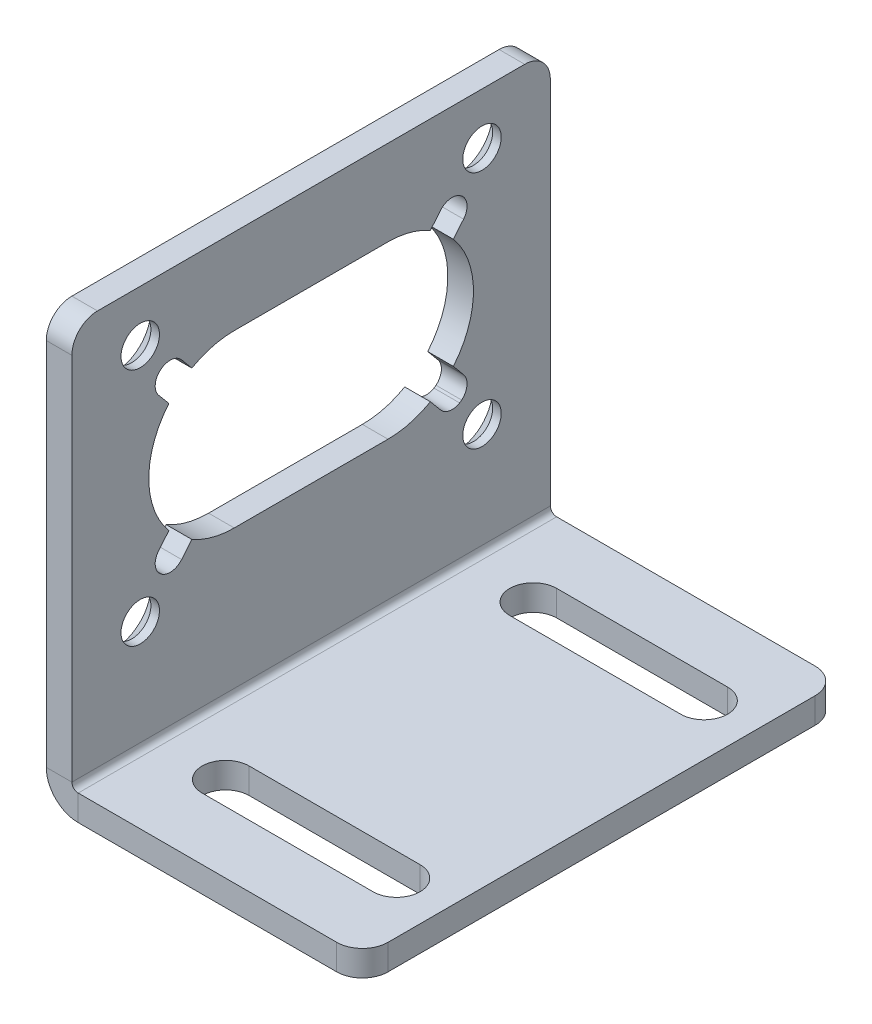
SolidWorks part; units mm, degrees
note: The reader was unsure of these and kept them because the rebuilt part matched: flange length of "Edge-Flange1".
material "0.6015 (EN-GJL-150)"
ref_plane "Front" through (0, 0, 0) normal (0, 0, 1) x (1, 0, 0)
ref_plane "Top" through (0, 0, 0) normal (0, 1, 0) x (1, 0, 0)
ref_plane "Right" through (0, 0, 0) normal (1, 0, 0) x (0, 0, -1)
sketch "Sketch1" plane through (0, 0, 0) normal (0, 1, 0) x (1, 0, 0)
  line L0 (-7.5, -18) -> (12.5, -18) construction
  line L1 (-18.5, 28) -> (15.5, 28)
  line L2 (-18.5, 28) -> (-18.5, -28)
  line L3 (-18.5, -28) -> (15.5, -28)
  line L4 (18.5, 25) -> (18.5, -25)
  line L5 (-18.5, 28) -> (18.5, -28) construction
  line L6 (-18.5, -28) -> (18.5, 28) construction
  line L7 (-7.5, -15.25) -> (12.5, -15.25)
  line L8 (-7.5, -20.75) -> (12.5, -20.75)
  line L9 (-54.4817, 0) -> (59.9128, 0) construction
  line L10 (-7.5, 18) -> (12.5, 18) construction
  line L11 (-7.5, 15.25) -> (12.5, 15.25)
  line L12 (-7.5, 20.75) -> (12.5, 20.75)
  arc A0 (15.5, -28) -> (18.5, -25) centre (15.5, -25) ccw
  arc A1 (15.5, 28) -> (18.5, 25) centre (15.5, 25) cw
  arc A2 (-7.5, -15.25) -> (-7.5, -20.75) centre (-7.5, -18) ccw
  arc A3 (12.5, -20.75) -> (12.5, -15.25) centre (12.5, -18) ccw
  arc A4 (-7.5, 15.25) -> (-7.5, 20.75) centre (-7.5, 18) cw
  arc A5 (12.5, 20.75) -> (12.5, 15.25) centre (12.5, 18) cw
  point P0 (0, 0)
  point P14 (2.5, -18)
  point P24 (2.5, 18)
  dimension "D3" = 3
  dimension "D1" = 37
  dimension "D2" = 56
  dimension "D4" = 36
  dimension "D5" = 5.5
  dimension "D6" = 20
  dimension "D7" = 11
base flange "Base-Flange1" sketch "Sketch1" thickness 3 reverse thickness direction no parameters "D1"=0.7366
edge flange "Edge-Flange1" sketch "Sketch4" flange angle 90 flange length 50 flange position material inside bend radius 0.7366 thickness 3 relief rectangular parameters "D6"=10
sketch "Sketch4" plane through (-18.5, 0, 0) normal (1, 0, 0) x (0, 0, -1)
  line L2 (-28, 0) -> (-28, 44)
  line L3 (-25, 47) -> (25, 47)
  line L4 (28, 44) -> (28, 0)
  line L5 (28, 0) -> (-28, 0) construction
  line L6 (28, 0) -> (-28, 0)
  line L7 (28, -3) -> (-28, -3) construction
  arc A0 (-28, 44) -> (-25, 47) centre (-25, 44) cw
  arc A1 (25, 47) -> (28, 44) centre (25, 44) cw
  dimension "D2" = 3
  dimension "D1" = 50
bend "EdgeBend1" bend radius 0.7366 bend angle 90 parameters "D5"=1
sketch "Sketch5" plane through (-18.5, 0, 0) normal (-1, 0, 0) x (0, 0, 1)
  line L0 (0, 58.9362) -> (0, -10.8221) construction
  line L1 (-37.9362, 27) -> (41.8892, 27) construction
  line L2 (-9, 27) -> (9, 27) construction
  line L3 (-9, 37) -> (9, 37)
  line L4 (-9, 17) -> (9, 17)
  line L5 (13.9587, 18.316) -> (15.1556, 16.8797)
  line L6 (28, -3) -> (-28, -3) construction
  line L7 (9, 27) -> (16.5, 36) construction
  line L8 (16.6474, 33.4433) -> (17.8444, 34.8797)
  line L9 (13.9587, 35.684) -> (15.1556, 37.1203)
  line L10 (16.6474, 20.5567) -> (17.8444, 19.1203)
  line L11 (-16.6474, 33.4433) -> (-17.8444, 34.8797)
  line L12 (-13.9587, 35.684) -> (-15.1556, 37.1203)
  line L13 (-13.9587, 18.316) -> (-15.1556, 16.8797)
  line L14 (-16.6474, 20.5567) -> (-17.8444, 19.1203)
  line L16 (-20, 41) -> (20, 41) construction
  line L17 (-20, 41) -> (-20, 13) construction
  line L18 (-20, 13) -> (20, 13) construction
  line L19 (20, 41) -> (20, 13) construction
  line L20 (-20, 41) -> (20, 13) construction
  line L21 (-20, 13) -> (20, 41) construction
  arc A0 (-9, 37) -> (-13.9587, 35.684) centre (-9, 27) ccw
  arc A1 (9, 17) -> (13.9587, 18.316) centre (9, 27) ccw
  arc A2 (17.8444, 34.8797) -> (15.1556, 37.1203) centre (16.5, 36) ccw
  arc A3 (17.8444, 19.1203) -> (15.1556, 16.8797) centre (16.5, 18) cw
  arc A5 (-17.8444, 19.1203) -> (-15.1556, 16.8797) centre (-16.5, 18) ccw
  arc A7 (13.9587, 35.684) -> (9, 37) centre (9, 27) ccw
  arc A9 (-13.9587, 18.316) -> (-9, 17) centre (-9, 27) ccw
  arc A10 (-17.8444, 34.8797) -> (-15.1556, 37.1203) centre (-16.5, 36) cw
  arc A11 (-16.6474, 33.4433) -> (-16.6474, 20.5567) centre (-9, 27) ccw
  arc A12 (16.6474, 20.5567) -> (16.6474, 33.4433) centre (9, 27) ccw
  circle A13 centre (20, 41) radius 2.25
  circle A14 centre (20, 41) radius 4.3619
  circle A15 centre (-20, 41) radius 2.25
  circle A16 centre (-20, 41) radius 4.3619
  circle A17 centre (-20, 13) radius 2.25
  circle A18 centre (-20, 13) radius 4.3619
  circle A19 centre (20, 13) radius 2.25
  circle A20 centre (20, 13) radius 4.3619
  point P7 (0, 27)
  point P12 (0, 27)
  point P41 (17.6203, 37.3444)
  dimension "D6" = 3.5
  dimension "D7" = 10
  dimension "D10" = 4.5
  dimension "D1" = 20
  dimension "D2" = 30
  dimension "D3" = 18
  dimension "D4" = 33
  dimension "D5" = 18
  dimension "D8" = 28
  dimension "D9" = 40
extrude "Cut-Extrude1" cut sketch "Sketch5" along direction (-1, 0, 0) on the side against the normal up to next (3 mm away) contours A20 A3 L10 A12 L8 A2 A14 L9 A7 L3 A0 L12 A10 A16 L11 A11 L14 A5 A18 L13 A9 L4 A1 L5 | A15 | A13 | A19 | A17 normal cut yes
chamfer "Chamfer1" distance 2 angle 45 4 edges at (-18.5, 38.75, -20) (-18.5, 10.75, -20) (-18.5, 10.75, 20) (-18.5, 38.75, 20)
sketch "Bend-Lines1" [suppressed] plane through (0, 0, 0) normal (0, 1, 0) x (1, 0, 0)
sketch "Bounding-Box1" [suppressed] plane through (0, 0, 0) normal (0, 1, 0) x (1, 0, 0)
sheet metal parameters "Sheet-Metal4" thickness 3 parameters "D1"=0.7366
flat pattern "Flat-Pattern4" [suppressed]
sketch "Bend-Lines2" plane through (0, 0, 0) normal (0, 1, 0) x (1, 0, 0)
sketch "Bounding-Box2" [suppressed] plane through (0, 0, 0) normal (0, 1, 0) x (1, 0, 0)
sheet metal parameters "Sheet-Metal6" thickness 3 parameters "D1"=0.7366
flat pattern "Flat-Pattern4" [suppressed]
sketch "Bend-Lines2" plane through (0, 0, 0) normal (0, 1, 0) x (1, 0, 0)
sketch "Bounding-Box2" [suppressed] plane through (0, 0, 0) normal (0, 1, 0) x (1, 0, 0)
bend of the flat pattern "Flatten-<EdgeBend1>1"
sheet metal parameters "Sheet-Metal7" thickness 3 parameters "D1"=0.7366
flat pattern "Flat-Pattern4"
sketch "Bend-Lines2" plane through (0, 0, 0) normal (0, 1, 0) x (1, 0, 0)
  line L0 (-16.52, 28) -> (-16.52, -28) construction
  line L1 (-16.52, 28) -> (-16.52, -28) construction
sketch3d "Bounding-Box2" [suppressed]
  line L0 (-80.04, -3, 0) -> (3, -3, 0) construction
  line L1 (-80.04, 53, 0) -> (3, 53, 0) construction
  line L2 (-80.04, -3, 0) -> (-80.04, 53, 0) construction
  line L3 (3, -3, 0) -> (3, 53, 0) construction
bend of the flat pattern "Flatten-<EdgeBend1>1"
